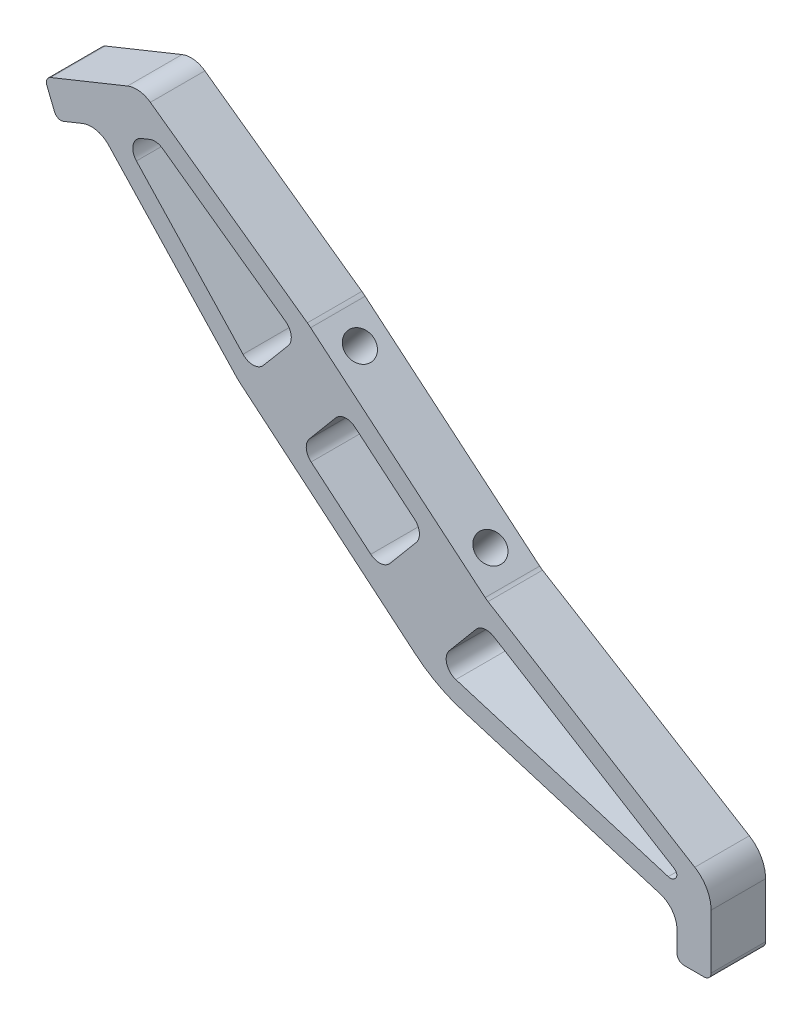
SolidWorks part; units mm, degrees
material "6061-T6 (SS)"
ref_plane "前视基准面" through (0, 0, 0) normal (0, 0, 1) x (1, 0, 0)
ref_plane "上视基准面" through (0, 0, 0) normal (0, 1, 0) x (1, 0, 0)
ref_plane "右视基准面" through (0, 0, 0) normal (1, 0, 0) x (0, 0, -1)
sketch "草图1" plane through (0, 0, 0) normal (0, 0, 1) x (1, 0, 0)
  line L0 (-18.5, 0) -> (18.5, 0) construction
  line L1 (0, 0) -> (0, 58) construction
  line L2 (-22, -3.5) -> (-22, -40.5) construction
  line L3 (-18.5, -44) -> (18.5, -44) construction
  line L4 (22, -40.5) -> (22, -3.5) construction
  line L5 (0, 58) -> (-18.9622, 35.4017) construction
  line L6 (-31.7681, 46.1471) -> (-6.1564, 24.6563)
  line L7 (-5.7348, 24.3529) -> (24.6118, 5.7637)
  line L8 (27, 1.5) -> (27, -6.5)
  line L9 (0, 58) -> (-53.7767, 36.2728) construction
  line L10 (-99.569, 41.4993) -> (-65.2632, 55.3597) construction
  line L11 (-60.7069, 53.4257) -> (-46.8464, 19.1199) construction
  line L12 (-48.7805, 14.5636) -> (-83.0863, 0.7032) construction
  line L13 (-87.6425, 2.6372) -> (-101.503, 36.943) construction
  line L14 (26, -7.5) -> (23, -7.5)
  line L15 (22, -6.5) -> (22, -3.5)
  line L16 (19.5166, -0.1509) -> (-9.5704, 8.6781)
  line L17 (-16.441, 12.3996) -> (-42.0527, 33.8904)
  line L18 (-32.251, 46.5218) -> (-55.2893, 63.0287)
  line L19 (-58.6389, 63.4288) -> (-69.9177, 58.8718)
  line L20 (-70.4703, 57.57) -> (-69.3465, 54.7885)
  line L21 (-68.0447, 54.2359) -> (-65.2632, 55.3597)
  line L22 (-61.3947, 54.5042) -> (-42.7557, 34.5568)
  line L23 (-38.8224, 31.1798) -> (-28.5378, 43.4365) construction
  line L24 (-19.6713, 15.1101) -> (-9.3867, 27.3668) construction
  line L25 (-33.6801, 37.3082) -> (-14.529, 21.2385) construction
  line L26 (-18.9622, 35.4017) -> (-24.1045, 29.2733) construction
  arc A0 (18.5, -44) -> (22, -40.5) centre (18.5, -40.5) ccw construction
  arc A1 (-22, -40.5) -> (-18.5, -44) centre (-18.5, -40.5) ccw construction
  arc A2 (18.5, 0) -> (22, -3.5) centre (18.5, -3.5) cw construction
  arc A3 (-18.5, 0) -> (-22, -3.5) centre (-18.5, -3.5) ccw construction
  arc A4 (-83.0863, 0.7032) -> (-87.6425, 2.6372) centre (-84.3974, 3.9483) cw construction
  arc A5 (-46.8464, 19.1199) -> (-48.7805, 14.5636) centre (-50.0916, 17.8088) cw construction
  arc A6 (-65.2632, 55.3597) -> (-60.7069, 53.4257) centre (-63.952, 52.1146) cw construction
  arc A7 (-99.569, 41.4993) -> (-101.503, 36.943) centre (-98.2578, 38.2542) ccw construction
  arc A8 (19.5166, -0.1509) -> (22, -3.5) centre (18.5, -3.5) cw
  arc A9 (24.6118, 5.7637) -> (27, 1.5) centre (22, 1.5) cw
  arc A10 (-6.1564, 24.6563) -> (-5.7348, 24.3529) centre (-3.9066, 27.3374) ccw
  arc A11 (-9.5704, 8.6781) -> (-16.441, 12.3996) centre (-3.9066, 27.3374) cw
  arc A12 (-65.2632, 55.3597) -> (-61.3947, 54.5042) centre (-63.952, 52.1146) cw
  arc A14 (-55.2893, 63.0287) -> (-58.6389, 63.4288) centre (-57.3278, 60.1836) ccw
  arc A15 (-42.0527, 33.8904) -> (-42.7557, 34.5568) centre (-36.9104, 40.0187) cw
  arc A16 (-31.7681, 46.1471) -> (-32.251, 46.5218) centre (-36.9104, 40.0187) ccw
  arc A21 (23, -7.5) -> (22, -6.5) centre (23, -6.5) cw
  arc A22 (27, -6.5) -> (26, -7.5) centre (26, -6.5) cw
  arc A23 (-69.9177, 58.8718) -> (-70.4703, 57.57) centre (-69.5431, 57.9447) ccw
  arc A24 (-69.3465, 54.7885) -> (-68.0447, 54.2359) centre (-68.4193, 55.1631) ccw
  point P13 (22, 0)
  point P16 (-22, 0)
  point P43 (-5.9569, 24.4889)
  point P56 (-32.0024, 46.3437)
  point P81 (22, -7.5)
  point P84 (27, -7.5)
  point P89 (-68.9719, 53.8613)
  dimension "D3" = 3.5
  dimension "D7" = 3.5
  dimension "D11" = 5
  dimension "D13" = 3.5
  dimension "D14" = 4
  dimension "D15" = 3.5
  dimension "D16" = 25
  dimension "D20" = 1
  dimension "D1" = 58
  dimension "D2" = 44
  dimension "D4" = 29.5
  dimension "D5" = 34
  dimension "D6" = 40
  dimension "D8" = 28
  dimension "D9" = 16
  dimension "D10" = 5
  dimension "D12" = 5
extrude "凸台-拉伸1" add sketch "草图1" along normal blind 8
sketch "草图2" plane through (-0.6874, -0.8192, 0) normal (-0.6428, -0.766, 0) x (0, 0, 1)
  line L0 (0, 49.7817) -> (8, 49.7817) construction
  line L1 (8, 53.9986) -> (8, 20.5648) construction
  line L2 (0, 24.7817) -> (8, 24.7817) construction
  circle A0 centre (4, 49.7817) radius 2.05
  circle A1 centre (4, 24.7817) radius 2.05
  dimension "D1" = 4.1
extrude "切除-拉伸1" cut sketch "草图2" against normal through all
sketch "Sketch1" plane through (0, 0, 8) normal (0, 0, 1) x (1, 0, 0)
  line L0 (22, 3.6537) -> (22, 3.8454)
  line L1 (-6.4068, 21.2464) -> (-13.3575, 12.9628)
  line L3 (-42.0527, 33.8904) -> (-16.441, 12.3996) construction
  line L4 (-33.6871, 43.8602) -> (-40.1481, 36.1602)
  line L5 (-40.1481, 36.1602) -> (-59.323, 56.6812)
  line L6 (-59.323, 56.6812) -> (-54.3725, 58.6813)
  line L7 (-61.3947, 54.5042) -> (-42.7557, 34.5568) construction
  line L8 (-58.6389, 63.4288) -> (-69.9177, 58.8718) construction
  line L9 (24.6118, 5.7637) -> (-5.7348, 24.3529) construction
  line L10 (-32.251, 46.5218) -> (-55.2893, 63.0287) construction
  line L11 (-54.3725, 58.6813) -> (-33.6871, 43.8602)
  line L12 (-26.8021, 38.0639) -> (-33.23, 30.4034)
  line L13 (-33.23, 30.4034) -> (-21.407, 20.4828)
  line L14 (-21.407, 20.4828) -> (-14.9791, 28.1432)
  line L15 (-6.1564, 24.6563) -> (-31.7681, 46.1471) construction
  line L16 (-26.8021, 38.0639) -> (-14.9791, 28.1432)
  line L17 (-13.3575, 12.9628) -> (22, 2.2305)
  line L18 (-6.4068, 21.2464) -> (22, 3.8454)
  line L19 (27, -6.5) -> (27, 1.5) construction
  line L21 (22, 3.6537) -> (22, 2.2305)
  line L23 (-9.5704, 8.6781) -> (19.5166, -0.1509) construction
  dimension "D1" = 3
  dimension "D3" = 6
  dimension "D4" = 3
  dimension "D5" = 3
  dimension "D6" = 3
  dimension "D8" = 3
  dimension "D9" = 3
  dimension "D10" = 3
  dimension "D12" = 5
  dimension "D13" = 3
  dimension "D14" = 3
  dimension "D15" = 5
extrude "Cut-Extrude1" cut sketch "Sketch1" against normal blind 10
fillet "Fillet1" radius 2 10 edges at (-6.4068, 21.2464, 4) (-13.3575, 12.9628, 4) (-33.23, 30.4034, 4) (-21.407, 20.4828, 4) (-14.9791, 28.1432, 4) (-26.8021, 38.0639, 4) (-59.323, 56.6812, 4) (-54.3725, 58.6813, 4) (-40.1481, 36.1602, 4) (-33.6871, 43.8602, 4)
fillet "Fillet2" radius 1 2 edges at (22, 2.2305, 4) (22, 3.8454, 4)
